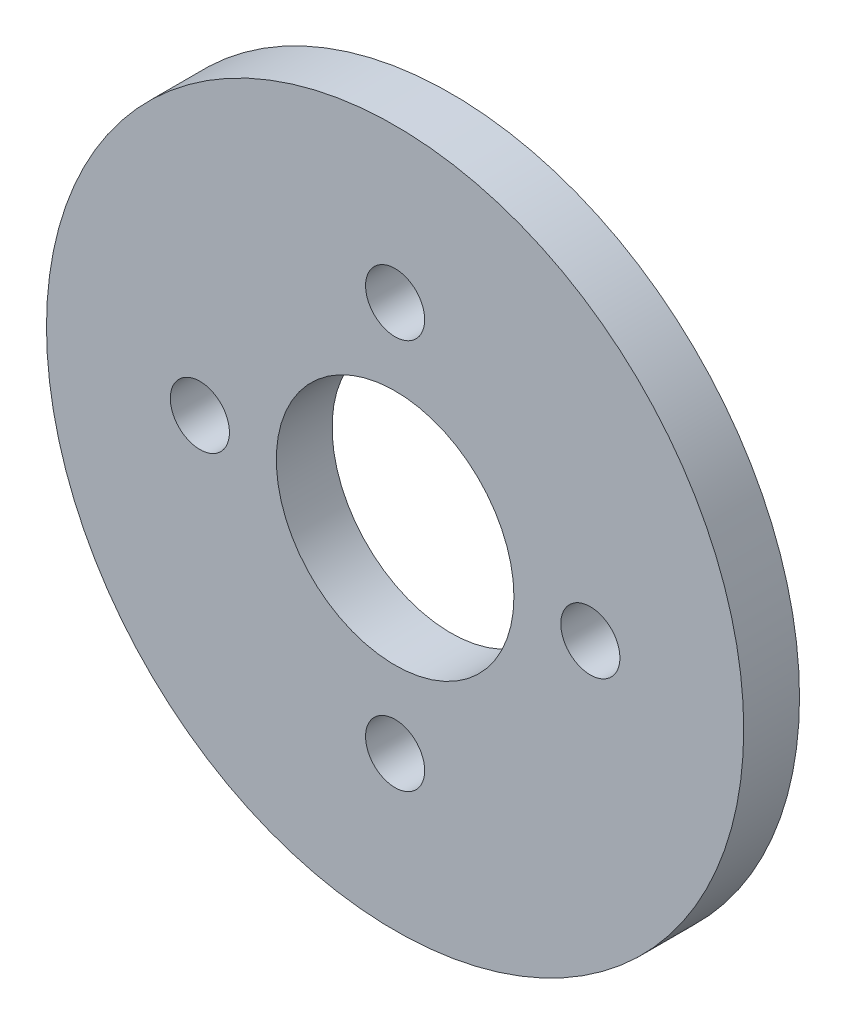
SolidWorks part; units mm, degrees
ref_plane "Płaszczyzna przednia" through (0, 0, 0) normal (0, 0, 1) x (1, 0, 0)
ref_plane "Płaszczyzna górna" through (0, 0, 0) normal (0, 1, 0) x (1, 0, 0)
ref_plane "Płaszczyzna prawa" through (0, 0, 0) normal (1, 0, 0) x (0, 0, -1)
sketch "Szkic1" plane through (0, 0, 0) normal (0, 0, 1) x (1, 0, 0)
  circle A0 centre (0, 0) radius 62.5
  circle A1 centre (0, 0) radius 35 construction
  circle A2 centre (0, 35) radius 5.3
  circle A3 centre (35, 0) radius 5.3
  circle A4 centre (0, -35) radius 5.3
  circle A5 centre (-35, 0) radius 5.3
  circle A6 centre (0, 0) radius 21.3
  dimension "D1" = 125
  dimension "D2" = 70
  dimension "D3" = 10.6
  dimension "D6" = 42.6
extrude "Dodanie-wyciągnięcie3" add sketch "Szkic1" along normal blind 10 contours A0 A5 A1 A2 A3 A4 | A5 A1 A4 A3 A2 A6 region at (-60.7322, 0, 0)
